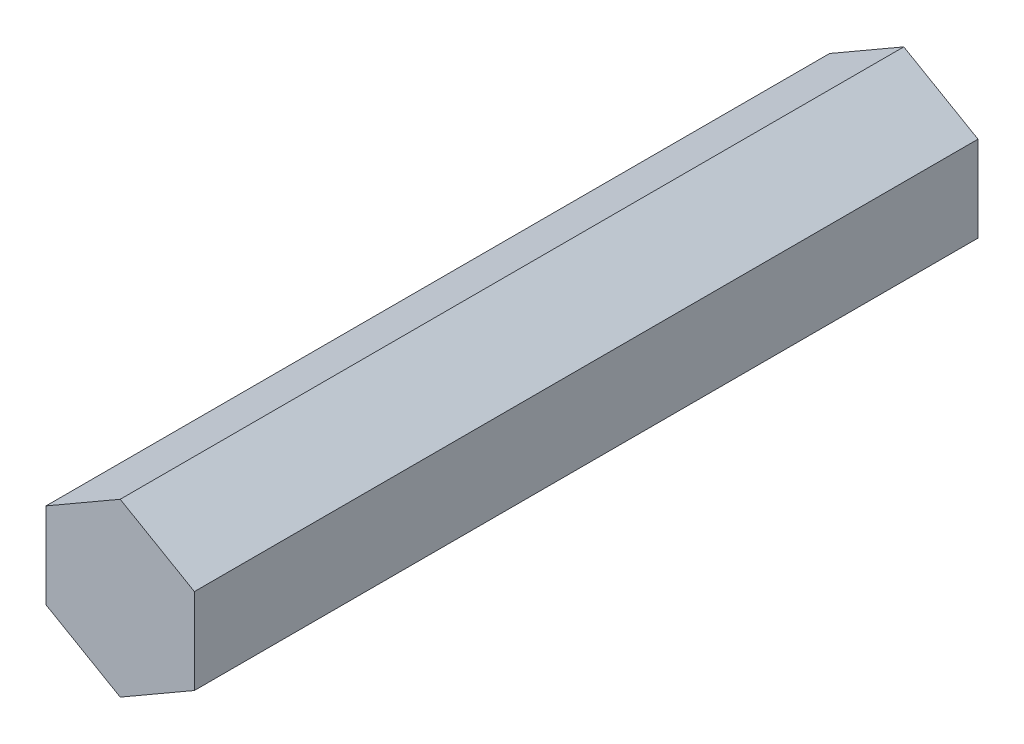
SolidWorks part; units mm, degrees
ref_plane "Front Plane" through (0, 0, 0) normal (0, 0, 1) x (1, 0, 0)
ref_plane "Top Plane" through (0, 0, 0) normal (0, 1, 0) x (1, 0, 0)
ref_plane "Right Plane" through (0, 0, 0) normal (1, 0, 0) x (0, 0, -1)
sketch "Sketch3" plane through (0, 0, 0) normal (1, 0, 0) x (0, 0, -1)
  line L0 (-28.575, 0) -> (28.575, 0) construction
  line L1 (0, 3.175) -> (0, -3.175) construction
  line L2 (-28.575, 1.7526) -> (-28.575, -1.7526) construction
  point P2 (19.05, 0)
  point P3 (-19.05, 0)
  dimension "Length" = 57.15
  dimension "Min Thread Length" = 9.525
  dimension "D1" = 9.525
  dimension "Thread Dia" = 3.5052
  dimension "Hex" = 6.35
sketch "Sketch1" plane through (0, 0, 0) normal (0, 0, 1) x (1, 0, 0)
  line L1 (0, 3.6662) -> (-3.175, 1.8331)
  line L2 (-3.175, 1.8331) -> (-3.175, -1.8331)
  line L3 (-3.175, -1.8331) -> (0, -3.6662)
  line L4 (0, -3.6662) -> (3.175, -1.8331)
  line L5 (3.175, -1.8331) -> (3.175, 1.8331)
  line L6 (3.175, 1.8331) -> (0, 3.6662)
  circle A0 centre (0, 0) radius 3.175 construction
  circle A1 centre (0, 0) radius 1.7526
extrude "Extrude1" add sketch "Sketch1" along normal up to vertex (28.575 mm away) and the other way up to vertex (28.575 mm away) up to point (0, 0, 28.575) other way up to point (0, 0, -28.575)
sketch "Sketch11" plane through (0, 0, -28.575) normal (0, 0, -1) x (-1, 0, 0)
  circle A0 centre (0, 0) radius 1.7526 construction
  circle A1 centre (0, 0) radius 1.7526
curve "Helix/Spiral1" pitch 0.7937 height 57.9437 radius 1.7526 centre (0, 0, -28.575) axis (0, 0, 1) start towards (0, 1, 0) parameters "Pitch"=0.7937
sketch "Sketch12" plane through (0, 0, 0) normal (1, 0, 0) x (0, 0, -1)
  line L0 (29.2695, 1.7526) -> (28.575, 1.7526)
  line L1 (29.2695, 1.7526) -> (28.9719, 1.237)
  line L2 (28.9719, 1.237) -> (28.8727, 1.237)
  line L3 (28.8727, 1.237) -> (28.575, 1.7526)
  line L4 (28.9223, 1.237) -> (28.9223, 1.7526) construction
  line L5 (29.1207, 1.4948) -> (28.7238, 1.4948) construction
  dimension "D1" = 0.0992
  dimension "D2" = 0.3969
  dimension "D3" = 60
sweep "Sweep1" add profiles "Sketch12" path "Helix/Spiral1"
sketch "Sketch6" plane through (0, 0, -28.575) normal (0, 0, -1) x (-1, 0, 0)
  line L6 (0, 3.6662) -> (-3.175, 1.8331)
  line L7 (-3.175, 1.8331) -> (-3.175, -1.8331)
  line L8 (-3.175, -1.8331) -> (0, -3.6662)
  line L9 (0, -3.6662) -> (3.175, -1.8331)
  line L10 (3.175, -1.8331) -> (3.175, 1.8331)
  line L11 (3.175, 1.8331) -> (0, 3.6662)
  line L12 (0, 3.6662) -> (-3.175, 1.8331)
  line L13 (-3.175, 1.8331) -> (-3.175, -1.8331)
  line L14 (-3.175, -1.8331) -> (0, -3.6662)
  line L15 (0, -3.6662) -> (3.175, -1.8331)
  line L16 (3.175, -1.8331) -> (3.175, 1.8331)
  line L17 (3.175, 1.8331) -> (0, 3.6662)
  dimension "D1" = 0
extrude "Extrude2" cut sketch "Sketch6" along normal through all
sketch "Sketch7" plane through (0, 0, -28.575) normal (0, 0, -1) x (-1, 0, 0)
  circle A2 centre (0, 0) radius 1.8034
  circle A3 centre (0, 0) radius 1.8034
  dimension "D1" = 0.0508
extrude "Extrude3" cut sketch "Sketch7" against normal through all draft 43
sketch "Sketch8" plane through (0, 0, -28.575) normal (0, 0, -1) x (-1, 0, 0)
  circle A0 centre (0, 0) radius 3.175 construction
  circle A1 centre (0, 0) radius 3.175
extrude "Extrude4" cut sketch "Sketch8" against normal through all draft 60 flip side to cut
mirror "Mirror1" about plane through (0, 0, 0) normal (0, 0, 1) of "Extrude2", "Extrude3", "Extrude4"
sketch "Sketch9" plane through (0, 0, 0) normal (1, 0, 0) x (0, 0, -1)
  line L1 (-19.05, 1.8034) -> (19.05, 1.8034)
  line L2 (-19.05, 1.8034) -> (-19.05, 0)
  line L3 (-19.05, 0) -> (19.05, 0)
  line L4 (19.05, 1.8034) -> (19.05, 0)
  line L7 (-28.575, 0) -> (28.575, 0) construction
revolve "Revolve" add sketch "Sketch9" angle 360 about L0
sketch "Sketch10" plane through (0, 0, 0) normal (1, 0, 0) x (0, 0, -1)
  line L0 (28.575, 1.7526) -> (19.05, 1.7526)
  line L1 (-28.575, 1.7526) -> (-19.05, 1.7526)
  line L2 (19.05, 1.7526) -> (19.05, -1.7526)
  line L3 (-28.575, -1.8034) -> (-19.05, -1.8034)
  line L4 (-19.05, 1.7526) -> (-19.05, -1.8034)
  line L5 (19.05, -1.7526) -> (28.575, -1.7526)
sketch "Sketch13" plane through (0, 0, 28.575) normal (0, 0, 1) x (1, 0, 0)
  circle A0 centre (0, 0) radius 3.6662
extrude "Cut-Extrude1" cut sketch "Sketch13" against normal blind 2.39
mirror "Mirror2" about plane through (0, 0, 0) normal (0, 0, 1) of "Cut-Extrude1"
ref_axis "Axis1" through (0, 0, 0) along (0, 0, 1)
sketch "Sketch14" plane through (0, 0, -26.185) normal (0, 0, -1) x (-1, 0, 0)
  circle A0 centre (0, 0) radius 3.6662
extrude "Cut-Extrude2" cut sketch "Sketch14" against normal offset from surface (9.421 mm away) 16.764 up to plane "Front Plane"
mirror "Mirror3" about plane through (0, 0, 0) normal (0, 0, 1) of "Cut-Extrude2"
equation "\"D1@Sketch3\" = \"Min Thread Length@Sketch3\""
equation "\"D3@Helix/Spiral1\" = \"Length@Sketch3\"+\"Pitch@Helix/Spiral1\""
equation "\"D1@Sketch12\" = \"Pitch@Helix/Spiral1\"*.125"
equation "\"D2@Sketch12\" = \"Pitch@Helix/Spiral1\"*.5"
